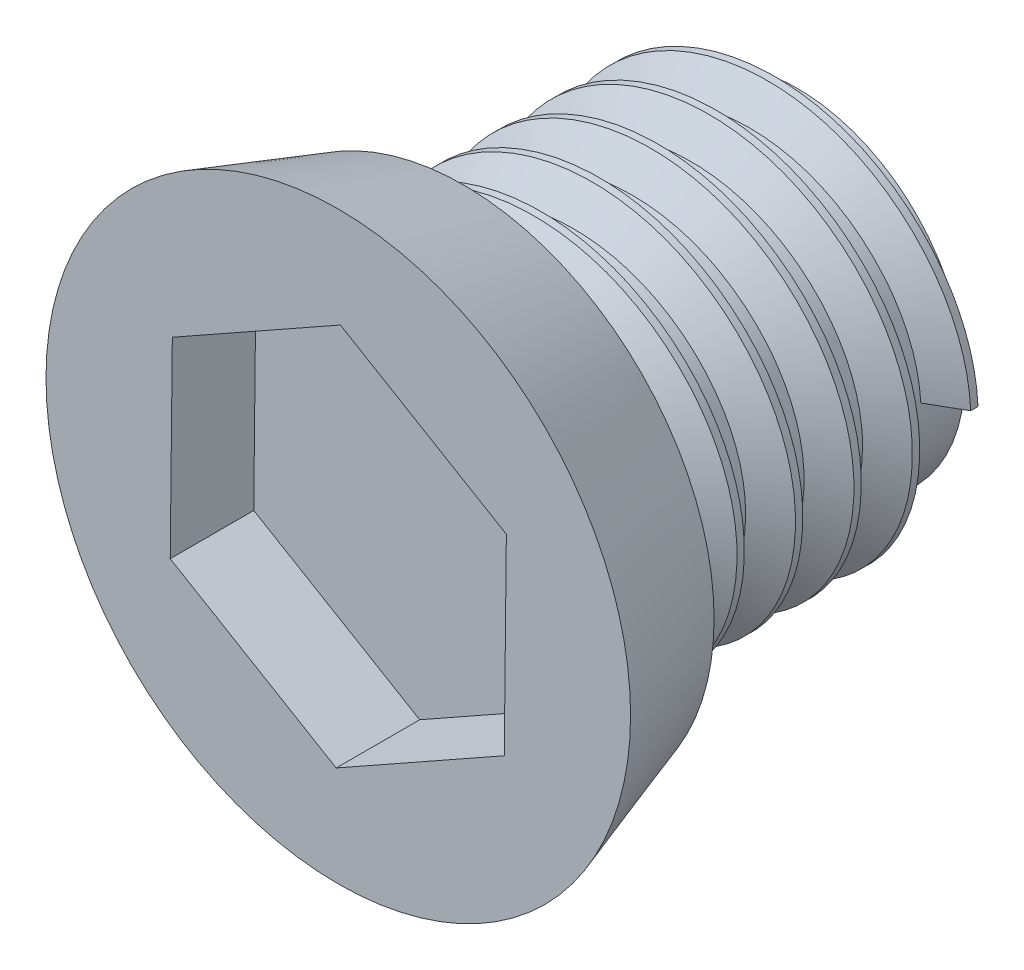
SolidWorks part; units mm, degrees
ref_plane "Front Plane" through (0, 0, 0) normal (0, 0, 1) x (1, 0, 0)
ref_plane "Top Plane" through (0, 0, 0) normal (0, 1, 0) x (1, 0, 0)
ref_plane "Right Plane" through (0, 0, 0) normal (1, 0, 0) x (0, 0, -1)
sketch "Sketch1" plane through (0, 0, 0) normal (0, 0, 1) x (1, 0, 0)
  circle A0 centre (0, 0) radius 2
  dimension "D1" = 4
extrude "Boss-Extrude1" add sketch "Sketch1" along normal blind 4
ref_plane "Plane1" through (0, 0, 5.5) normal (0, 0, 1) x (1, 0, 0)
sketch "Sketch3" plane through (0, 0, 5.5) normal (0, 0, 1) x (1, 0, 0)
  circle A0 centre (0, 0) radius 3.5
  dimension "D1" = 7
sketch "Sketch4" plane through (0, 0, 4) normal (0, 0, 1) x (1, 0, 0)
  circle A0 centre (0, 0) radius 3
  dimension "D1" = 6
loft "Loft2" add profiles "Sketch4", "Sketch3" connector at (-2.0632, 2.1779, 4) connector at (-2.2747, 2.66, 5.5)
thread "Thread1" pitch 0.7 method extrude profile "Thread Profile1" start angle 0, offset 0, length 0, pitch 0.7, diameter 4
ref_plane "Plane2" through (2, 0, 0) normal (0, -1, 0) x (1, 0, 0)
sketch "Thread Profile1" plane through (2, 0, 0) normal (0, -1, 0) x (1, 0, 0)
  line L0 (0, 0) -> (0, 0.7) construction
  line L1 (0, 0) -> (0.3789, 0.2187)
  line L2 (0.3789, 0.2187) -> (0.3789, 0.3062)
  line L3 (0.3789, 0.3062) -> (0, 0.525)
  line L4 (0.3789, 0.2625) -> (0, 0.2625) construction
  line L11 (0, 0) -> (0, 0.525)
  point P2 (0, 0)
  dimension "Pitch" = 0.7
  dimension "Profile_Angle" = 60
  dimension "Profile_Land" = 0.0875
  dimension "Profile_Height" = 0.3789
sketch "Sketch7" plane through (0, 0, 5.5) normal (0, 0, 1) x (1, 0, 0)
  line L1 (2.0124, 1.1329) -> (0.0251, 2.3093)
  line L2 (0.0251, 2.3093) -> (-1.9873, 1.1764)
  line L3 (-1.9873, 1.1764) -> (-2.0124, -1.1329)
  line L4 (-2.0124, -1.1329) -> (-0.0251, -2.3093)
  line L5 (-0.0251, -2.3093) -> (1.9873, -1.1764)
  line L6 (1.9873, -1.1764) -> (2.0124, 1.1329)
  circle A0 centre (0, 0) radius 2 construction
  dimension "D1" = 4
extrude "Cut-Extrude1" cut sketch "Sketch7" against normal blind 1 contours L3 L4 L5 L6 L1 L2
